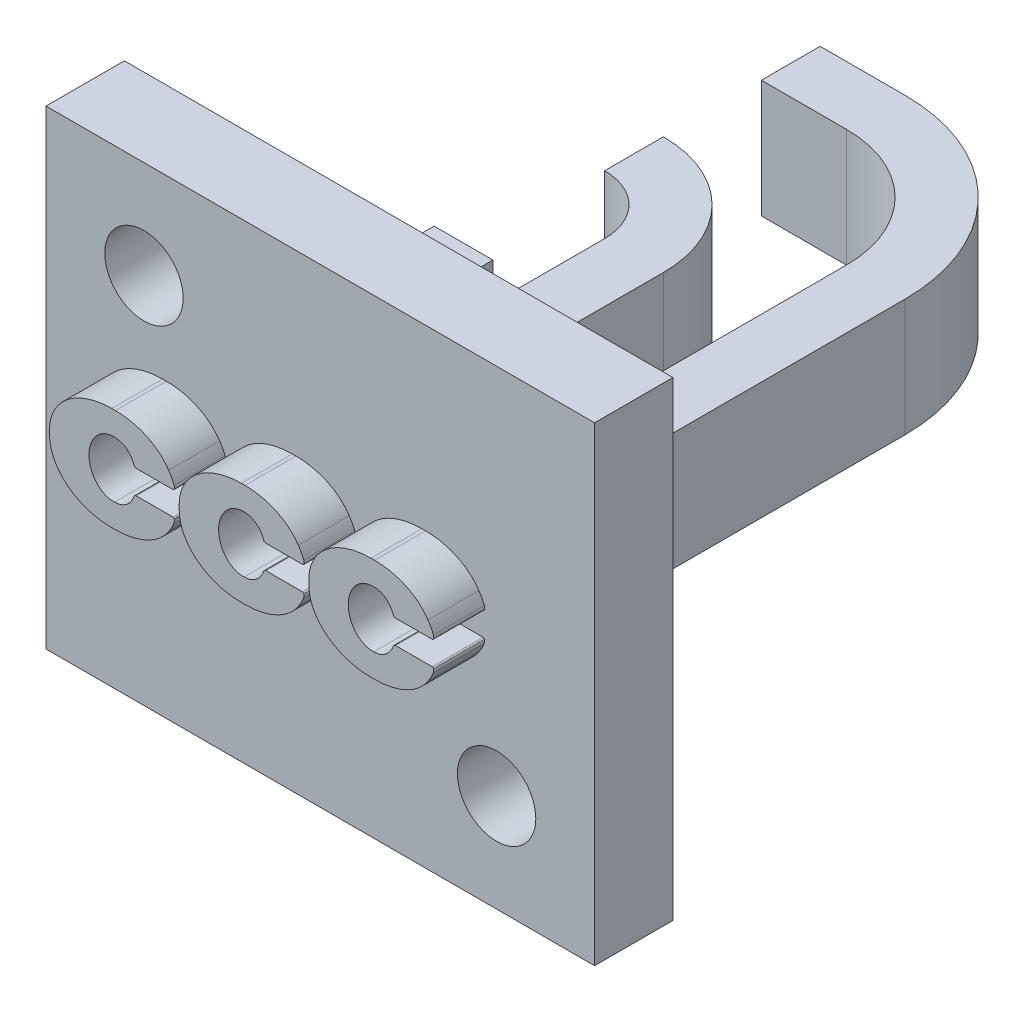
SolidWorks part; units mm, degrees
ref_plane "Front Plane" through (0, 0, 0) normal (0, 0, 1) x (1, 0, 0)
ref_plane "Top Plane" through (0, 0, 0) normal (0, 1, 0) x (1, 0, 0)
ref_plane "Right Plane" through (0, 0, 0) normal (1, 0, 0) x (0, 0, -1)
sketch "Sketch1" plane through (0, 0, 0) normal (0, 0, 1) x (1, 0, 0)
  line L1 (-7.5, 6) -> (7.5, 6)
  line L2 (-7.5, 6) -> (-7.5, -6)
  line L3 (-7.5, -6) -> (7.5, -6)
  line L4 (7.5, 6) -> (7.5, -6)
  line L5 (-7.5, 6) -> (7.5, -6) construction
  line L6 (-7.5, -6) -> (7.5, 6) construction
  point P0 (0, 0)
  dimension "D1" = 15
  dimension "D2" = 12
extrude "Boss-Extrude1" add sketch "Sketch1" along normal blind 2
sketch "Sketch2" plane through (0, 0, 2) normal (0, 0, 1) x (1, 0, 0)
  line L0 (-0.5835, 0.4438) -> (0.3524, 0.4438)
  line L1 (-1.1209, 1.4546) -> (-1.2145, 1.4546)
  line L2 (-2.8001, 0.2034) -> (-2.8001, 0.0733)
  line L3 (-1.2145, -1.1779) -> (-1.1209, -1.1779)
  line L4 (0.3478, -0.1633) -> (-0.5835, -0.1633)
  line L5 (-3.8918, 0.4438) -> (-2.956, 0.4438)
  line L6 (-4.4292, 1.4546) -> (-4.5228, 1.4546)
  line L7 (-6.1084, 0.2034) -> (-6.1084, 0.0733)
  line L8 (-4.5228, -1.1779) -> (-4.4292, -1.1779)
  line L9 (-2.9605, -0.1633) -> (-3.8918, -0.1633)
  line L10 (2.7248, 0.4438) -> (3.6607, 0.4438)
  line L11 (2.1874, 1.4546) -> (2.0938, 1.4546)
  line L12 (0.5082, 0.2034) -> (0.5082, 0.0733)
  line L13 (2.0938, -1.1779) -> (2.1874, -1.1779)
  line L14 (3.6561, -0.1633) -> (2.7248, -0.1633)
  arc A0 (-0.6452, 0.4874) -> (-0.5835, 0.4438) centre (-0.5835, 0.5092) ccw
  arc A1 (0.3524, 0.4438) -> (0.3816, 0.4686) centre (0.3479, 0.4787) ccw
  arc A2 (0.3816, 0.4686) -> (0.3774, 0.5561) centre (0.201, 0.5038) ccw
  arc A3 (0.3774, 0.5561) -> (0.2402, 0.8134) centre (-0.7046, 0.1445) ccw
  arc A4 (0.2402, -0.5368) -> (0.3727, -0.2904) centre (-0.6952, 0.1249) ccw
  arc A5 (0.3727, -0.2904) -> (0.3825, -0.1925) centre (0.2012, -0.2237) ccw
  arc A6 (0.3825, -0.1925) -> (0.3478, -0.1633) centre (0.3478, -0.1984) ccw
  arc A7 (-0.5835, -0.1633) -> (-0.6452, -0.2069) centre (-0.5835, -0.2287) ccw
  arc A8 (-3.9535, 0.4874) -> (-3.8918, 0.4438) centre (-3.8918, 0.5092) ccw
  arc A9 (-2.956, 0.4438) -> (-2.9267, 0.4686) centre (-2.9604, 0.4787) ccw
  arc A10 (-2.9267, 0.4686) -> (-2.9309, 0.5561) centre (-3.1073, 0.5038) ccw
  arc A11 (-2.9309, 0.5561) -> (-3.0681, 0.8134) centre (-4.0129, 0.1445) ccw
  arc A12 (-3.0681, -0.5368) -> (-2.9356, -0.2904) centre (-4.0035, 0.1249) ccw
  arc A13 (-2.9356, -0.2904) -> (-2.9258, -0.1925) centre (-3.1071, -0.2237) ccw
  arc A14 (-2.9258, -0.1925) -> (-2.9605, -0.1633) centre (-2.9605, -0.1984) ccw
  arc A15 (-3.8918, -0.1633) -> (-3.9535, -0.2069) centre (-3.8918, -0.2287) ccw
  arc A16 (2.6631, 0.4874) -> (2.7248, 0.4438) centre (2.7248, 0.5092) ccw
  arc A17 (3.6607, 0.4438) -> (3.6899, 0.4686) centre (3.6562, 0.4787) ccw
  arc A18 (3.6899, 0.4686) -> (3.6857, 0.5561) centre (3.5093, 0.5038) ccw
  arc A19 (3.6857, 0.5561) -> (3.5485, 0.8134) centre (2.6037, 0.1445) ccw
  arc A20 (3.5485, -0.5368) -> (3.681, -0.2904) centre (2.6131, 0.1249) ccw
  arc A21 (3.681, -0.2904) -> (3.6908, -0.1925) centre (3.5095, -0.2237) ccw
  arc A22 (3.6908, -0.1925) -> (3.6561, -0.1633) centre (3.6561, -0.1984) ccw
  arc A23 (2.7248, -0.1633) -> (2.6631, -0.2069) centre (2.7248, -0.2287) ccw
  ellipse E0 centre (-1.1734, 0.1385) end of major axis (-1.177, 0.8556) minor radius 0.6209 (-1.2015, 0.8549) -> (-1.1417, -0.5777) ccw
  ellipse E1 centre (-1.2295, 0.1385) end of major axis (-1.5121, -0.5431) minor radius 0.6039 (-0.6452, 0.4874) -> (-1.2015, 0.8549) ccw
  ellipse E2 centre (-1.2429, 0.1529) end of major axis (-2.8857, -0.0922) minor radius 1.2925 (0.2402, 0.8134) -> (-1.1209, 1.4546) ccw
  ellipse E3 centre (-1.1521, 0.1542) end of major axis (0.4928, 0.0248) minor radius 1.2979 (-1.2145, 1.4546) -> (-2.8001, 0.2034) ccw
  ellipse E4 centre (-1.1521, 0.1225) end of major axis (0.4928, 0.2518) minor radius 1.2979 (-2.8001, 0.0733) -> (-1.2145, -1.1779) ccw
  ellipse E5 centre (-1.2429, 0.1238) end of major axis (-2.8857, 0.3689) minor radius 1.2925 (-1.1209, -1.1779) -> (0.2402, -0.5368) ccw
  ellipse E6 centre (-1.2295, 0.1421) end of major axis (-0.9469, -0.5396) minor radius 0.6039 (-1.1417, -0.5777) -> (-0.6452, -0.2069) ccw
  ellipse E7 centre (-4.5378, 0.1385) end of major axis (-4.8204, -0.5431) minor radius 0.6039 (-3.9535, 0.4874) -> (-4.5098, 0.8549) ccw
  ellipse E8 centre (-4.5512, 0.1529) end of major axis (-6.194, -0.0922) minor radius 1.2925 (-3.0681, 0.8134) -> (-4.4292, 1.4546) ccw
  ellipse E9 centre (-4.4604, 0.1542) end of major axis (-6.1053, 0.2835) minor radius 1.2979 (-4.5228, 1.4546) -> (-6.1084, 0.2034) ccw
  ellipse E10 centre (-4.4604, 0.1225) end of major axis (-6.1053, -0.0069) minor radius 1.2979 (-6.1084, 0.0733) -> (-4.5228, -1.1779) ccw
  ellipse E11 centre (-4.5512, 0.1238) end of major axis (-6.194, 0.3689) minor radius 1.2925 (-4.4292, -1.1779) -> (-3.0681, -0.5368) ccw
  ellipse E12 centre (-4.5378, 0.1421) end of major axis (-4.2552, -0.5396) minor radius 0.6039 (-4.45, -0.5777) -> (-3.9535, -0.2069) ccw
  ellipse E13 centre (-4.4817, 0.1385) end of major axis (-4.4853, 0.8556) minor radius 0.6209 (-4.5098, 0.8549) -> (-4.45, -0.5777) ccw
  ellipse E14 centre (2.1349, 0.1385) end of major axis (2.1385, -0.5786) minor radius 0.6209 (2.1069, 0.8549) -> (2.1666, -0.5777) ccw
  ellipse E15 centre (2.0788, 0.1385) end of major axis (2.3614, 0.8201) minor radius 0.6039 (2.6631, 0.4874) -> (2.1069, 0.8549) ccw
  ellipse E16 centre (2.0654, 0.1529) end of major axis (3.7082, 0.3981) minor radius 1.2925 (3.5485, 0.8134) -> (2.1874, 1.4546) ccw
  ellipse E17 centre (2.1562, 0.1542) end of major axis (0.5113, 0.2835) minor radius 1.2979 (2.0938, 1.4546) -> (0.5082, 0.2034) ccw
  ellipse E18 centre (2.1562, 0.1225) end of major axis (3.8011, 0.2518) minor radius 1.2979 (0.5082, 0.0733) -> (2.0938, -1.1779) ccw
  ellipse E19 centre (2.0654, 0.1238) end of major axis (0.4226, 0.3689) minor radius 1.2925 (2.1874, -1.1779) -> (3.5485, -0.5368) ccw
  ellipse E20 centre (2.0788, 0.1421) end of major axis (2.3614, -0.5396) minor radius 0.6039 (2.1666, -0.5777) -> (2.6631, -0.2069) ccw
extrude "Boss-Extrude2" add sketch "Sketch2" along normal blind 2
sketch "Sketch3" plane through (0, 0, 0) normal (0, 1, 0) x (1, 0, 0)
  line L0 (7.5, 0) -> (-7.5, 0) construction
  line L1 (1.7287, 0) -> (3.2287, 0)
  line L2 (1.7287, 0) -> (1.7287, 12.2)
  line L3 (-3.644, -2) -> (-3.644, 5.3789) construction
  line L4 (3.2287, 0) -> (3.2287, 13.7)
  line L5 (-4.394, 0) -> (-2.894, 0)
  line L6 (-4.394, 0) -> (-4.394, 4.8)
  line L7 (-1.1926, -2) -> (-1.1926, 4.6797) construction
  line L8 (-2.894, 0) -> (-2.894, 4.8)
  line L9 (-2.894, 4.8) -> (-4.394, 4.8)
  line L10 (-1.9426, 0) -> (-0.4426, 0)
  line L13 (-1.9426, 0) -> (-1.9426, 8.2)
  line L14 (2.4787, -2) -> (2.4787, 2.787) construction
  line L15 (-0.4426, 0) -> (-0.4426, 9.7)
  line L16 (-0.4426, 9.7) -> (-3.4426, 9.7)
  line L17 (-3.4426, 13.7) -> (3.2287, 13.7)
  line L18 (-1.9426, 8.2) -> (-3.4426, 8.2)
  line L19 (-3.4426, 9.7) -> (-3.4426, 8.2)
  line L20 (-3.4426, 13.7) -> (-3.4426, 12.2)
  line L21 (-3.4426, 12.2) -> (1.7287, 12.2)
  dimension "D1" = 1.5
  dimension "D2" = 4.8
  dimension "D3" = 1.5
  dimension "D4" = 1.5
  dimension "D5" = 8.2
  dimension "D6" = 1.5
  dimension "D7" = 2.5
  dimension "D8" = 1.5
  dimension "D9" = 1.5
  dimension "D10" = 3.644
  dimension "D11" = 1.1926
  dimension "D12" = 2.4787
extrude "Boss-Extrude3" add sketch "Sketch3" along normal mid plane 3
fillet "Fillet3" radius 1.5 1 edges at (-1.9426, 0, -8.2)
fillet "Fillet4" radius 3 1 edges at (-0.4426, 0, -9.7)
fillet "Fillet5" radius 3 1 edges at (1.7287, 0, -12.2)
fillet "Fillet6" radius 4.5 1 edges at (3.2287, 0, -13.7)
sketch "Sketch4" plane through (7.5, 0, 0) normal (1, 0, 0) x (0, 0, -1)
  line L4 (0, -6) -> (0, 6)
  line L5 (0, 6) -> (-2, 6)
  line L6 (-2, 6) -> (-2, -6)
  line L7 (-2, -6) -> (0, -6)
  line L8 (0, -6) -> (0, 6)
  line L9 (0, 6) -> (-2, 6)
  line L10 (-2, 6) -> (-2, -6)
  line L11 (-2, -6) -> (0, -6)
  dimension "D1" = 0
extrude "Cut-Extrude1" cut sketch "Sketch4" against normal blind 1
sketch "Sketch5" plane through (0, 0, 0) normal (0, 0, -1) x (-1, 0, 0)
  line L0 (-6.5, -6) -> (-6.5, 6) construction
  line L1 (7.5, -6) -> (-6.5, -6) construction
  line L2 (7.5, 6) -> (7.5, -6) construction
  line L3 (-6.5, 6) -> (7.5, 6) construction
  circle A0 centre (-4, -3.5) radius 1
  circle A1 centre (5, 3.5) radius 1
  dimension "D1" = 2
  dimension "D2" = 2.5
  dimension "D3" = 2.5
  dimension "D4" = 2.5
  dimension "D5" = 2.5
extrude "Cut-Extrude2" cut sketch "Sketch5" against normal through all
sketch "Sketch6" plane through (0, 0, 4) normal (0, 0, 1) x (1, 0, 0)
  line L0 (2.7248, 0.4438) -> (3.6607, 0.4438) construction
  line L1 (2.1874, 1.4546) -> (2.0938, 1.4546) construction
  line L2 (0.5082, 0.2034) -> (0.5082, 0.0733) construction
  line L3 (2.0938, -1.1779) -> (2.1874, -1.1779) construction
  line L4 (3.6561, -0.1633) -> (2.7248, -0.1633) construction
  line L5 (-0.5835, 0.4438) -> (0.3524, 0.4438) construction
  line L6 (-1.1209, 1.4546) -> (-1.2145, 1.4546) construction
  line L7 (-2.8001, 0.2034) -> (-2.8001, 0.0733) construction
  line L8 (-1.2145, -1.1779) -> (-1.1209, -1.1779) construction
  line L9 (0.3478, -0.1633) -> (-0.5835, -0.1633) construction
  line L10 (-3.8918, 0.4438) -> (-2.956, 0.4438) construction
  line L11 (-4.4292, 1.4546) -> (-4.5228, 1.4546) construction
  line L12 (-6.1084, 0.2034) -> (-6.1084, 0.0733) construction
  line L13 (-4.5228, -1.1779) -> (-4.4292, -1.1779) construction
  line L14 (-2.9605, -0.1633) -> (-3.8918, -0.1633) construction
  line L15 (2.7248, 0.4438) -> (3.6607, 0.4438)
  line L16 (2.1874, 1.4546) -> (2.0938, 1.4546)
  line L17 (0.5082, 0.2034) -> (0.5082, 0.0733)
  line L18 (2.0938, -1.1779) -> (2.1874, -1.1779)
  line L19 (3.6561, -0.1633) -> (2.7248, -0.1633)
  line L20 (-0.5835, 0.4438) -> (0.3524, 0.4438)
  line L21 (-1.1209, 1.4546) -> (-1.2145, 1.4546)
  line L22 (-2.8001, 0.2034) -> (-2.8001, 0.0733)
  line L23 (-1.2145, -1.1779) -> (-1.1209, -1.1779)
  line L24 (0.3478, -0.1633) -> (-0.5835, -0.1633)
  line L25 (-3.8918, 0.4438) -> (-2.956, 0.4438)
  line L26 (-4.4292, 1.4546) -> (-4.5228, 1.4546)
  line L27 (-6.1084, 0.2034) -> (-6.1084, 0.0733)
  line L28 (-4.5228, -1.1779) -> (-4.4292, -1.1779)
  line L29 (-2.9605, -0.1633) -> (-3.8918, -0.1633)
  arc A0 (2.6631, 0.4874) -> (2.7248, 0.4438) centre (2.7248, 0.5092) ccw construction
  arc A1 (3.6607, 0.4438) -> (3.6899, 0.4686) centre (3.6562, 0.4787) ccw construction
  arc A2 (3.6899, 0.4686) -> (3.6857, 0.5561) centre (3.5093, 0.5038) ccw construction
  arc A3 (3.6857, 0.5561) -> (3.5485, 0.8134) centre (2.6037, 0.1445) ccw construction
  arc A4 (3.5485, -0.5368) -> (3.681, -0.2904) centre (2.6131, 0.1249) ccw construction
  arc A5 (3.681, -0.2904) -> (3.6908, -0.1925) centre (3.5095, -0.2237) ccw construction
  arc A6 (3.6908, -0.1925) -> (3.6561, -0.1633) centre (3.6561, -0.1984) ccw construction
  arc A7 (2.7248, -0.1633) -> (2.6631, -0.2069) centre (2.7248, -0.2287) ccw construction
  arc A8 (-0.6452, 0.4874) -> (-0.5835, 0.4438) centre (-0.5835, 0.5092) ccw construction
  arc A9 (0.3524, 0.4438) -> (0.3816, 0.4686) centre (0.3479, 0.4787) ccw construction
  arc A10 (0.3816, 0.4686) -> (0.3774, 0.5561) centre (0.201, 0.5038) ccw construction
  arc A11 (0.3774, 0.5561) -> (0.2402, 0.8134) centre (-0.7046, 0.1445) ccw construction
  arc A12 (0.2402, -0.5368) -> (0.3727, -0.2904) centre (-0.6952, 0.1249) ccw construction
  arc A13 (0.3727, -0.2904) -> (0.3825, -0.1925) centre (0.2012, -0.2237) ccw construction
  arc A14 (0.3825, -0.1925) -> (0.3478, -0.1633) centre (0.3478, -0.1984) ccw construction
  arc A15 (-0.5835, -0.1633) -> (-0.6452, -0.2069) centre (-0.5835, -0.2287) ccw construction
  arc A16 (-3.9535, 0.4874) -> (-3.8918, 0.4438) centre (-3.8918, 0.5092) ccw construction
  arc A17 (-2.956, 0.4438) -> (-2.9267, 0.4686) centre (-2.9604, 0.4787) ccw construction
  arc A18 (-2.9267, 0.4686) -> (-2.9309, 0.5561) centre (-3.1073, 0.5038) ccw construction
  arc A19 (-2.9309, 0.5561) -> (-3.0681, 0.8134) centre (-4.0129, 0.1445) ccw construction
  arc A20 (-3.0681, -0.5368) -> (-2.9356, -0.2904) centre (-4.0035, 0.1249) ccw construction
  arc A21 (-2.9356, -0.2904) -> (-2.9258, -0.1925) centre (-3.1071, -0.2237) ccw construction
  arc A22 (-2.9258, -0.1925) -> (-2.9605, -0.1633) centre (-2.9605, -0.1984) ccw construction
  arc A23 (-3.8918, -0.1633) -> (-3.9535, -0.2069) centre (-3.8918, -0.2287) ccw construction
  arc A24 (2.6631, 0.4874) -> (2.7248, 0.4438) centre (2.7248, 0.5092) ccw
  arc A25 (3.6607, 0.4438) -> (3.6899, 0.4686) centre (3.6562, 0.4787) ccw
  arc A26 (3.6899, 0.4686) -> (3.6857, 0.5561) centre (3.5093, 0.5038) ccw
  arc A27 (3.6857, 0.5561) -> (3.5485, 0.8134) centre (2.6037, 0.1445) ccw
  arc A28 (3.5485, -0.5368) -> (3.681, -0.2904) centre (2.6131, 0.1249) ccw
  arc A29 (3.681, -0.2904) -> (3.6908, -0.1925) centre (3.5095, -0.2237) ccw
  arc A30 (3.6908, -0.1925) -> (3.6561, -0.1633) centre (3.6561, -0.1984) ccw
  arc A31 (2.7248, -0.1633) -> (2.6631, -0.2069) centre (2.7248, -0.2287) ccw
  arc A32 (-0.6452, 0.4874) -> (-0.5835, 0.4438) centre (-0.5835, 0.5092) ccw
  arc A33 (0.3524, 0.4438) -> (0.3816, 0.4686) centre (0.3479, 0.4787) ccw
  arc A34 (0.3816, 0.4686) -> (0.3774, 0.5561) centre (0.201, 0.5038) ccw
  arc A35 (0.3774, 0.5561) -> (0.2402, 0.8134) centre (-0.7046, 0.1445) ccw
  arc A36 (0.2402, -0.5368) -> (0.3727, -0.2904) centre (-0.6952, 0.1249) ccw
  arc A37 (0.3727, -0.2904) -> (0.3825, -0.1925) centre (0.2012, -0.2237) ccw
  arc A38 (0.3825, -0.1925) -> (0.3478, -0.1633) centre (0.3478, -0.1984) ccw
  arc A39 (-0.5835, -0.1633) -> (-0.6452, -0.2069) centre (-0.5835, -0.2287) ccw
  arc A40 (-3.9535, 0.4874) -> (-3.8918, 0.4438) centre (-3.8918, 0.5092) ccw
  arc A41 (-2.956, 0.4438) -> (-2.9267, 0.4686) centre (-2.9604, 0.4787) ccw
  arc A42 (-2.9267, 0.4686) -> (-2.9309, 0.5561) centre (-3.1073, 0.5038) ccw
  arc A43 (-2.9309, 0.5561) -> (-3.0681, 0.8134) centre (-4.0129, 0.1445) ccw
  arc A44 (-3.0681, -0.5368) -> (-2.9356, -0.2904) centre (-4.0035, 0.1249) ccw
  arc A45 (-2.9356, -0.2904) -> (-2.9258, -0.1925) centre (-3.1071, -0.2237) ccw
  arc A46 (-2.9258, -0.1925) -> (-2.9605, -0.1633) centre (-2.9605, -0.1984) ccw
  arc A47 (-3.8918, -0.1633) -> (-3.9535, -0.2069) centre (-3.8918, -0.2287) ccw
  ellipse E0 centre (2.0788, 0.1385) end of major axis (1.7962, -0.5431) minor radius 0.6039 (2.6631, 0.4874) -> (2.1069, 0.8549) ccw construction
  ellipse E1 centre (2.0654, 0.1529) end of major axis (0.4226, -0.0922) minor radius 1.2925 (3.5485, 0.8134) -> (2.1874, 1.4546) ccw construction
  ellipse E2 centre (2.1562, 0.1542) end of major axis (0.5113, 0.2835) minor radius 1.2979 (2.0938, 1.4546) -> (0.5082, 0.2034) ccw construction
  ellipse E3 centre (2.1562, 0.1225) end of major axis (3.8011, 0.2518) minor radius 1.2979 (0.5082, 0.0733) -> (2.0938, -1.1779) ccw construction
  ellipse E4 centre (2.0654, 0.1238) end of major axis (0.4226, 0.3689) minor radius 1.2925 (2.1874, -1.1779) -> (3.5485, -0.5368) ccw construction
  ellipse E5 centre (2.0788, 0.1421) end of major axis (2.3614, -0.5396) minor radius 0.6039 (2.1666, -0.5777) -> (2.6631, -0.2069) ccw construction
  ellipse E6 centre (2.1349, 0.1385) end of major axis (2.1385, -0.5786) minor radius 0.6209 (2.1069, 0.8549) -> (2.1666, -0.5777) ccw construction
  ellipse E7 centre (-1.2295, 0.1385) end of major axis (-1.5121, -0.5431) minor radius 0.6039 (-0.6452, 0.4874) -> (-1.2015, 0.8549) ccw construction
  ellipse E8 centre (-1.2429, 0.1529) end of major axis (0.3999, 0.3981) minor radius 1.2925 (0.2402, 0.8134) -> (-1.1209, 1.4546) ccw construction
  ellipse E9 centre (-1.1521, 0.1542) end of major axis (-2.797, 0.2835) minor radius 1.2979 (-1.2145, 1.4546) -> (-2.8001, 0.2034) ccw construction
  ellipse E10 centre (-1.1521, 0.1225) end of major axis (0.4928, 0.2518) minor radius 1.2979 (-2.8001, 0.0733) -> (-1.2145, -1.1779) ccw construction
  ellipse E11 centre (-1.2429, 0.1238) end of major axis (0.3999, -0.1214) minor radius 1.2925 (-1.1209, -1.1779) -> (0.2402, -0.5368) ccw construction
  ellipse E12 centre (-1.2295, 0.1421) end of major axis (-0.9469, -0.5396) minor radius 0.6039 (-1.1417, -0.5777) -> (-0.6452, -0.2069) ccw construction
  ellipse E13 centre (-1.1734, 0.1385) end of major axis (-1.1698, -0.5786) minor radius 0.6209 (-1.2015, 0.8549) -> (-1.1417, -0.5777) ccw construction
  ellipse E14 centre (-4.5378, 0.1385) end of major axis (-4.8204, -0.5431) minor radius 0.6039 (-3.9535, 0.4874) -> (-4.5098, 0.8549) ccw construction
  ellipse E15 centre (-4.5512, 0.1529) end of major axis (-2.9084, 0.3981) minor radius 1.2925 (-3.0681, 0.8134) -> (-4.4292, 1.4546) ccw construction
  ellipse E16 centre (-4.4604, 0.1542) end of major axis (-6.1053, 0.2835) minor radius 1.2979 (-4.5228, 1.4546) -> (-6.1084, 0.2034) ccw construction
  ellipse E17 centre (-4.4604, 0.1225) end of major axis (-2.8155, 0.2518) minor radius 1.2979 (-6.1084, 0.0733) -> (-4.5228, -1.1779) ccw construction
  ellipse E18 centre (-4.5512, 0.1238) end of major axis (-6.194, 0.3689) minor radius 1.2925 (-4.4292, -1.1779) -> (-3.0681, -0.5368) ccw construction
  ellipse E19 centre (-4.5378, 0.1421) end of major axis (-4.2552, -0.5396) minor radius 0.6039 (-4.45, -0.5777) -> (-3.9535, -0.2069) ccw construction
  ellipse E20 centre (-4.4817, 0.1385) end of major axis (-4.4781, -0.5786) minor radius 0.6209 (-4.5098, 0.8549) -> (-4.45, -0.5777) ccw construction
  ellipse E21 centre (2.0788, 0.1385) end of major axis (1.7962, -0.5431) minor radius 0.6039 (2.6631, 0.4874) -> (2.1069, 0.8549) ccw
  ellipse E22 centre (2.0654, 0.1529) end of major axis (3.7082, 0.3981) minor radius 1.2925 (3.5485, 0.8134) -> (2.1874, 1.4546) ccw
  ellipse E23 centre (2.1562, 0.1542) end of major axis (0.5113, 0.2835) minor radius 1.2979 (2.0938, 1.4546) -> (0.5082, 0.2034) ccw
  ellipse E24 centre (2.1562, 0.1225) end of major axis (3.8011, 0.2518) minor radius 1.2979 (0.5082, 0.0733) -> (2.0938, -1.1779) ccw
  ellipse E25 centre (2.0654, 0.1238) end of major axis (0.4226, 0.3689) minor radius 1.2925 (2.1874, -1.1779) -> (3.5485, -0.5368) ccw
  ellipse E26 centre (2.0788, 0.1421) end of major axis (2.3614, -0.5396) minor radius 0.6039 (2.1666, -0.5777) -> (2.6631, -0.2069) ccw
  ellipse E27 centre (2.1349, 0.1385) end of major axis (2.1385, -0.5786) minor radius 0.6209 (2.1069, 0.8549) -> (2.1666, -0.5777) ccw
  ellipse E28 centre (-1.2295, 0.1385) end of major axis (-1.5121, -0.5431) minor radius 0.6039 (-0.6452, 0.4874) -> (-1.2015, 0.8549) ccw
  ellipse E29 centre (-1.2429, 0.1529) end of major axis (0.3999, 0.3981) minor radius 1.2925 (0.2402, 0.8134) -> (-1.1209, 1.4546) ccw
  ellipse E30 centre (-1.1521, 0.1542) end of major axis (-2.797, 0.2835) minor radius 1.2979 (-1.2145, 1.4546) -> (-2.8001, 0.2034) ccw
  ellipse E31 centre (-1.1521, 0.1225) end of major axis (0.4928, 0.2518) minor radius 1.2979 (-2.8001, 0.0733) -> (-1.2145, -1.1779) ccw
  ellipse E32 centre (-1.2429, 0.1238) end of major axis (-2.8857, 0.3689) minor radius 1.2925 (-1.1209, -1.1779) -> (0.2402, -0.5368) ccw
  ellipse E33 centre (-1.2295, 0.1421) end of major axis (-0.9469, -0.5396) minor radius 0.6039 (-1.1417, -0.5777) -> (-0.6452, -0.2069) ccw
  ellipse E34 centre (-1.1734, 0.1385) end of major axis (-1.1698, -0.5786) minor radius 0.6209 (-1.2015, 0.8549) -> (-1.1417, -0.5777) ccw
  ellipse E35 centre (-4.5378, 0.1385) end of major axis (-4.8204, -0.5431) minor radius 0.6039 (-3.9535, 0.4874) -> (-4.5098, 0.8549) ccw
  ellipse E36 centre (-4.5512, 0.1529) end of major axis (-2.9084, 0.3981) minor radius 1.2925 (-3.0681, 0.8134) -> (-4.4292, 1.4546) ccw
  ellipse E37 centre (-4.4604, 0.1542) end of major axis (-6.1053, 0.2835) minor radius 1.2979 (-4.5228, 1.4546) -> (-6.1084, 0.2034) ccw
  ellipse E38 centre (-4.4604, 0.1225) end of major axis (-2.8155, 0.2518) minor radius 1.2979 (-6.1084, 0.0733) -> (-4.5228, -1.1779) ccw
  ellipse E39 centre (-4.5512, 0.1238) end of major axis (-6.194, 0.3689) minor radius 1.2925 (-4.4292, -1.1779) -> (-3.0681, -0.5368) ccw
  ellipse E40 centre (-4.5378, 0.1421) end of major axis (-4.2552, -0.5396) minor radius 0.6039 (-4.45, -0.5777) -> (-3.9535, -0.2069) ccw
  ellipse E41 centre (-4.4817, 0.1385) end of major axis (-4.4781, -0.5786) minor radius 0.6209 (-4.5098, 0.8549) -> (-4.45, -0.5777) ccw
extrude "Cut-Extrude3" cut sketch "Sketch6" against normal blind 0.7
